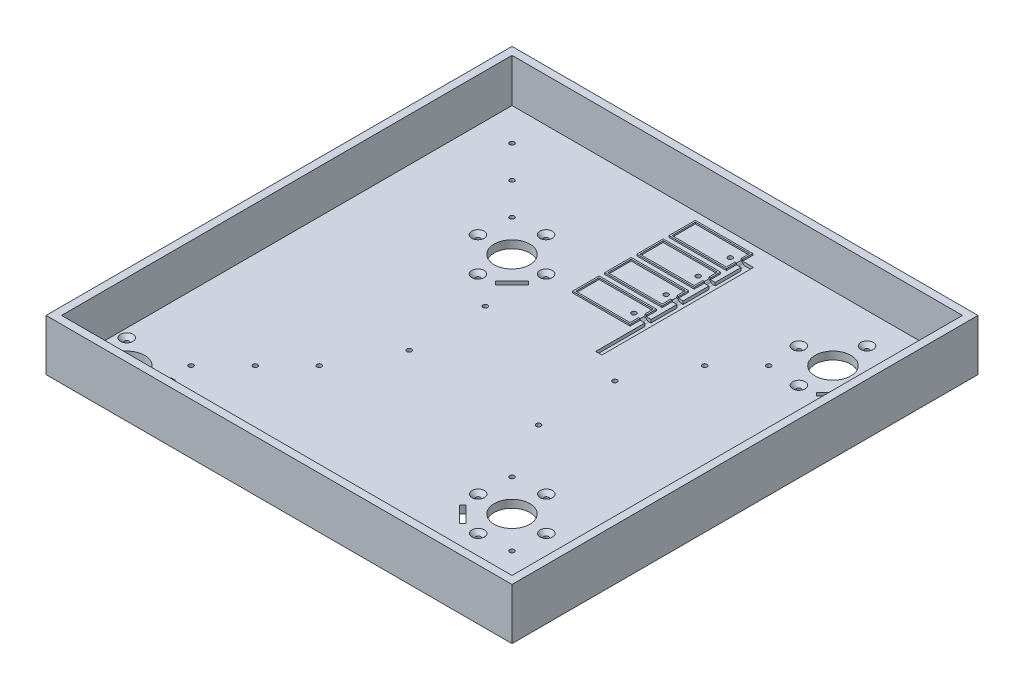
SolidWorks part; units mm, degrees
note: The reader was unsure of these and kept them because the rebuilt part matched: shared geometry of "Эскиз8<2>".
material "ABS"
ref_plane "Спереди" through (0, 0, 0) normal (0, 0, 1) x (1, 0, 0)
ref_plane "Сверху" through (0, 0, 0) normal (0, 1, 0) x (1, 0, 0)
ref_plane "Справа" through (0, 0, 0) normal (1, 0, 0) x (0, 0, -1)
other "Configuration Table"
sketch "Эскиз1" plane through (0, 0, 0) normal (0, 1, 0) x (1, 0, 0)
  line L0 (-136.1102, 103.5232) -> (-30.3617, 103.5232) construction
  line L1 (-136.1102, 103.5232) -> (163.8898, 103.5232)
  line L2 (-136.1102, 103.5232) -> (-136.1102, -196.4768)
  line L3 (-136.1102, -196.4768) -> (163.8898, -196.4768)
  line L4 (163.8898, 103.5232) -> (163.8898, -196.4768)
  line L5 (-136.1102, 103.5232) -> (-136.1102, -1.4471) construction
  line L8 (-30.5081, -2.079) -> (-35385.8471, 35353.2601) construction
  line L9 (-136.1102, 98.5232) -> (163.8898, 98.5232) construction
  line L10 (-131.1102, 103.5232) -> (-131.1102, -196.4768) construction
  line L11 (158.8898, 103.5232) -> (158.8898, -196.4768) construction
  line L12 (-136.1102, -191.4768) -> (163.8898, -191.4768) construction
  line L17 (-36.1102, 3.5232) -> (-131.1102, 3.5232) construction
  line L18 (-36.1102, 3.5232) -> (63.8898, 3.5232) construction
  line L19 (-36.1102, 3.5232) -> (-36.1102, -96.4768) construction
  line L20 (-36.1102, -96.4768) -> (63.8898, -96.4768) construction
  line L21 (63.8898, 3.5232) -> (63.8898, -96.4768) construction
  line L22 (-36.1102, -96.4768) -> (-131.1102, -96.4768) construction
  line L23 (-36.1102, 3.5232) -> (-36.1102, 98.5232) construction
  line L24 (63.8898, 3.5232) -> (158.8898, 3.5232) construction
  line L25 (63.8898, -96.4768) -> (158.8898, -96.4768) construction
  line L26 (63.8898, 3.5232) -> (63.8898, 98.5232) construction
  line L27 (63.8898, -96.4768) -> (63.8898, -191.4768) construction
  line L32 (-837.8814, -898.248) -> (34517.4576, 34457.0911) construction
  line L33 (-131.1102, -191.4768) -> (-89.1102, -149.4768) construction
  line L35 (-131.1102, -149.4768) -> (-131.1102, -191.4768) construction
  line L36 (-131.1102, -191.4768) -> (-89.1102, -191.4768) construction
  line L38 (-36.1102, -96.4768) -> (-36.1102, -191.4768) construction
  line L39 (-131.1102, -149.4768) -> (-89.1102, -149.4768) construction
  line L44 (-89.1102, -191.4768) -> (-89.1102, -149.4768) construction
  line L45 (-131.1102, -149.4768) -> (-89.1102, -191.4768) construction
  line L54 (-77.8295, 15.544) -> (-48.1311, 45.2425) construction
  line L71 (-48.1311, 45.2425) -> (-18.4326, 15.544) construction
  line L72 (-18.4326, 15.544) -> (-48.1311, -14.1545) construction
  line L73 (-77.8295, 15.544) -> (-48.1311, -14.1545) construction
  line L74 (-48.1311, -14.1545) -> (-48.1311, 45.2425) construction
  line L75 (-77.8295, 15.544) -> (-17.684, 15.544) construction
  line L76 (-48.1311, 22.044) -> (75.9106, 22.044) construction
  line L77 (-68.7786, 42.6915) -> (96.5581, 42.6915) construction
  line L78 (-89.4261, 63.339) -> (117.2056, 63.339) construction
  line L79 (-110.1092, 84.0221) -> (137.7881, 84.0211) construction
  line L80 (-33.2818, 0.6948) -> (-38.5851, -4.6085)
  line L81 (-38.5851, -4.6085) -> (-36.4638, -6.7299)
  line L86 (-27.9785, 5.9981) -> (-33.2818, 0.6948)
  line L91 (66.8596, -128.9763) -> (96.5581, -99.2778) construction
  line L97 (66.8596, -128.9763) -> (96.5581, -158.6748) construction
  line L98 (96.5581, -99.2778) -> (126.2566, -128.9763) construction
  line L99 (96.5581, -158.6748) -> (126.2566, -128.9763) construction
  line L100 (96.5581, -158.6748) -> (96.5581, -99.2778) construction
  line L101 (66.8596, -128.9763) -> (126.2566, -128.9763) construction
  line L102 (81.7088, -143.8256) -> (76.8333, -138.95)
  line L103 (76.8333, -138.95) -> (74.712, -141.0714)
  line L105 (74.712, -141.0714) -> (80.0153, -146.3747)
  line L106 (81.7088, -143.8256) -> (87.0121, -149.1289)
  line L107 (87.0121, -149.1289) -> (84.8908, -151.2502)
  line L108 (80.0153, -146.3747) -> (84.8908, -151.2502)
  line L109 (87.5071, 56.839) -> (117.2056, 86.5375) construction
  line L110 (87.5071, 56.839) -> (117.2056, 27.1406) construction
  line L111 (117.2056, 27.1406) -> (146.9041, 56.839) construction
  line L112 (146.9041, 56.839) -> (117.2056, 86.5375) construction
  line L113 (87.5071, 56.839) -> (146.9041, 56.839) construction
  line L114 (117.2056, 27.1406) -> (117.2056, 86.5375) construction
  line L115 (132.0548, 41.9898) -> (126.7515, 36.6865)
  line L116 (126.7515, 36.6865) -> (128.8729, 34.5652)
  line L117 (128.8729, 34.5652) -> (134.1762, 39.8685)
  line L119 (132.0548, 41.9898) -> (137.3581, 47.2931)
  line L120 (139.4795, 45.1718) -> (134.1762, 39.8685)
  line L121 (137.3581, 47.2931) -> (139.4795, 45.1718)
  line L122 (-89.1102, -170.4768) -> (-89.1102, -162.9768)
  line L123 (-89.1102, -162.9768) -> (-86.1102, -162.9768)
  line L124 (-86.1102, -162.9768) -> (-86.1102, -168.2374)
  line L125 (-86.1102, -168.2374) -> (-86.1102, -177.9768)
  line L126 (-86.1102, -177.9768) -> (-89.1102, -177.9768)
  line L127 (-89.1102, -177.9768) -> (-89.1102, -170.4768)
  line L128 (-36.4638, -6.7299) -> (-25.8572, 3.8767)
  line L129 (-30.7602, -73.9968) -> (58.5398, -73.9968) construction
  line L130 (-30.7602, -73.9968) -> (-30.7602, -18.9568) construction
  line L131 (-30.7602, -18.9568) -> (58.5398, -18.9568) construction
  line L132 (58.5398, -73.9968) -> (58.5398, -18.9568) construction
  line L133 (-30.7602, -73.9968) -> (58.5398, -18.9568) construction
  line L134 (-30.7602, -18.9568) -> (58.5398, -73.9968) construction
  line L135 (-25.8572, 3.8767) -> (-27.9785, 5.9981)
  line L136 (82.4106, 15.544) -> (82.4106, -108.4976) construction
  line L137 (103.0581, 36.1915) -> (103.0559, -128.9763) construction
  line L138 (123.7056, 56.839) -> (123.7056, -149.7927) construction
  line L139 (144.3885, 77.5219) -> (144.3885, -170.4755) construction
  line L140 (-48.1311, -114.9976) -> (75.9106, -114.9976) construction
  line L141 (-68.7786, -135.6451) -> (96.5581, -135.6451) construction
  line L142 (-89.4261, -156.2927) -> (117.2056, -156.2927) construction
  line L143 (-110.1102, -176.9768) -> (137.8885, -176.9755) construction
  line L144 (-54.6311, 15.544) -> (-54.6311, -108.4976) construction
  line L145 (-75.2786, 36.1915) -> (-75.2786, -129.1451) construction
  line L146 (-95.9261, 56.839) -> (-95.9184, -149.4768) construction
  line L147 (-116.6092, 77.5221) -> (-116.6092, -170.5948) construction
  line L148 (-1.1106, 84.0217) -> (-1.1106, 76.5217) construction
  line L157 (-1.1102, 29.544) -> (28.8898, 29.544) construction
  line L159 (-1.1102, 29.544) -> (-1.1102, 14.544) construction
  line L160 (-1.1102, 14.544) -> (28.8898, 14.544) construction
  line L161 (28.8898, 29.544) -> (28.8898, 14.544) construction
  line L162 (-1.1106, 50.1915) -> (28.8894, 50.1915) construction
  line L163 (-1.1106, 50.1915) -> (-1.1106, 35.1915) construction
  line L164 (-1.1106, 35.1915) -> (28.8894, 35.1915) construction
  line L165 (28.8894, 50.1915) -> (28.8894, 35.1915) construction
  line L166 (-1.1106, 70.839) -> (28.8894, 70.839) construction
  line L167 (-1.1106, 70.839) -> (-1.1106, 55.839) construction
  line L168 (-1.1106, 55.839) -> (28.8894, 55.839) construction
  line L169 (28.8894, 70.839) -> (28.8894, 55.839) construction
  line L174 (-1.1106, 84.0217) -> (-1.1106, 91.5217) construction
  line L175 (-1.1106, 91.5217) -> (28.8894, 91.5217) construction
  line L176 (28.8894, 91.5217) -> (28.8894, 76.5217) construction
  line L177 (28.8894, 76.5217) -> (-1.1106, 76.5217) construction
  line L178 (-131.1102, -86.4768) -> (-36.1102, -86.4768) construction
  line L179 (-131.1102, -76.4768) -> (-36.1102, -76.4768) construction
  line L180 (-131.1102, -66.4768) -> (-36.1102, -66.4768) construction
  line L181 (-131.1102, -56.4768) -> (-36.1102, -56.4768) construction
  line L182 (-131.1102, -46.4768) -> (-36.1102, -46.4768) construction
  line L183 (-131.1102, -36.4768) -> (-36.1102, -36.4768) construction
  line L184 (-131.1102, -26.4768) -> (-36.1102, -26.4768) construction
  line L185 (-131.1102, -16.4768) -> (-36.1102, -16.4768) construction
  line L186 (-131.1102, -6.4768) -> (-36.1102, -6.4768) construction
  circle A49 centre (-48.1311, 15.544) radius 11.5
  circle A51 centre (-89.4261, 56.839) radius 1.5
  circle A52 centre (-110.1092, 77.5221) radius 1.5
  circle A53 centre (-110.1102, -170.4768) radius 11.5
  circle A54 centre (-125.6102, -154.9768) radius 1.5
  circle A55 centre (-125.6102, -185.9768) radius 1.5
  circle A56 centre (-94.6102, -185.9768) radius 1.5
  circle A57 centre (-89.4261, -149.7927) radius 1.5
  circle A58 centre (-68.7786, -129.1451) radius 1.5
  circle A59 centre (-48.1311, -108.4976) radius 1.5
  circle A60 centre (-110.1102, -170.4768) radius 6.5 construction
  circle A61 centre (-48.1311, -108.4976) radius 6.5 construction
  circle A62 centre (-68.7786, -129.1451) radius 6.5 construction
  circle A63 centre (-89.4261, -149.7927) radius 6.5 construction
  circle A64 centre (-48.1311, 15.544) radius 6.5 construction
  circle A65 centre (-68.7786, 36.1915) radius 1.5
  circle A66 centre (-68.7786, 36.1915) radius 6.5 construction
  circle A67 centre (-89.4261, 56.839) radius 6.5 construction
  circle A68 centre (-110.1092, 77.5221) radius 6.5 construction
  circle A69 centre (-48.1311, 37.4643) radius 1.5
  circle A70 centre (-70.0514, 15.544) radius 1.5
  circle A71 centre (-26.2108, 15.544) radius 1.5
  circle A72 centre (-48.1311, -6.3763) radius 1.5
  circle A73 centre (75.9106, -108.4976) radius 1.5
  circle A74 centre (96.5581, -129.1451) radius 11.5
  circle A75 centre (117.2056, -149.7927) radius 1.5
  circle A76 centre (137.8885, -170.4755) radius 1.5
  circle A77 centre (75.9106, -108.4976) radius 6.5 construction
  circle A78 centre (96.5581, -129.1451) radius 6.5 construction
  circle A79 centre (117.2056, -149.7927) radius 6.5 construction
  circle A80 centre (137.8885, -170.4755) radius 6.5 construction
  circle A81 centre (96.5581, -107.056) radius 1.5
  circle A82 centre (74.6378, -128.9763) radius 1.5
  circle A83 centre (96.5581, -150.8966) radius 1.5
  circle A84 centre (118.4784, -128.9763) radius 1.5
  circle A85 centre (75.9106, 15.544) radius 1.5
  circle A86 centre (96.5581, 36.1915) radius 1.5
  circle A87 centre (117.2056, 56.839) radius 11.5
  circle A88 centre (137.8885, 77.5219) radius 1.5
  circle A89 centre (75.9106, 15.544) radius 6.5 construction
  circle A90 centre (96.5581, 36.1915) radius 6.5 construction
  circle A91 centre (137.8885, 77.5219) radius 6.5 construction
  circle A92 centre (117.2056, 78.7594) radius 1.5
  circle A93 centre (95.2853, 56.839) radius 1.5
  circle A94 centre (139.1259, 56.839) radius 1.5
  circle A95 centre (117.2056, 34.9187) radius 1.5
  circle A96 centre (-27.7602, -21.9568) radius 1.5
  circle A97 centre (-27.7602, -70.9968) radius 1.5
  circle A98 centre (55.5398, -70.9968) radius 1.5
  circle A99 centre (55.5398, -21.9568) radius 1.5
  circle A100 centre (117.2056, 56.839) radius 6.5 construction
  circle A101 centre (23.8894, 84.0216) radius 1.5
  circle A102 centre (23.8894, 63.339) radius 1.5
  circle A103 centre (23.8894, 42.6915) radius 1.5
  circle A104 centre (23.8898, 22.044) radius 1.5
  point P20 (-131.1102, 98.5232)
  point P43 (-110.1102, -170.4768)
  point P65 (-48.1311, 15.544)
  point P72 (158.8898, 98.5232)
  point P76 (158.8898, -191.4768)
  point P113 (96.5581, -128.9763)
  point P146 (117.2056, 56.839)
  point P168 (13.8898, -46.4768)
  point P169 (13.8898, -46.4768)
  point P214 (12.3478, 20.3373)
  dimension "D5" = 100
  dimension "D17" = 95
  dimension "D29" = 5.5
  dimension "D31" = 5.5
  dimension "D33" = 17
  dimension "D36" = 21
  dimension "D50" = 29.2503
  dimension "D51" = 5.5
  dimension "D53" = 5.5
  dimension "D54" = 5.5
  dimension "D65" = 7.5
  dimension "D67" = 3
  dimension "D69" = 29.2
  dimension "D71" = 29.25
  dimension "D80" = 0
  dimension "D84" = 5.5
  dimension "D112" = 5.5
  dimension "D116" = 3
  dimension "D9" = 42
  dimension "D26" = 5.5
  dimension "D28" = 5.5
  dimension "D30" = 5.5
  dimension "D32" = 17
  dimension "D34" = 29.7
  dimension "D55" = 5.5
  dimension "D57" = 5.5
  dimension "D68" = 17
  dimension "D72" = 42
  dimension "D81" = 5.5
  dimension "D83" = 5.5
  dimension "D85" = 5.5
  dimension "D87" = 5.5
  dimension "D92" = 17
  dimension "D96" = 0
  dimension "D105" = 5.5
  dimension "D108" = 5.5
  dimension "D110" = 5.5
  dimension "D122" = 3
  dimension "D124" = 3
  dimension "D126" = 3
  dimension "D128" = 3
  dimension "D131" = 13
  dimension "D132" = 13
  dimension "D133" = 13
  dimension "D134" = 13
  dimension "D135" = 13
  dimension "D136" = 13
  dimension "D137" = 13
  dimension "D138" = 13
  dimension "D139" = 13
  dimension "D140" = 13
  dimension "D141" = 13
  dimension "D142" = 13
  dimension "D143" = 13
  dimension "D144" = 13
  dimension "D145" = 13
  dimension "D146" = 13
  dimension "D162" = 5
  dimension "D163" = 5
  dimension "D164" = 5
  dimension "D165" = 5
  dimension "D1" = 300
  dimension "D2" = 300
  dimension "D3" = 5
  dimension "D4" = 5
  dimension "D6" = 5
  dimension "D7" = 5
  dimension "D8" = 100
  dimension "D10" = 42
  dimension "D11" = 21
  dimension "D12" = 5
  dimension "D13" = 5
  dimension "D15" = 95
  dimension "D18" = 95
  dimension "D19" = 95
  dimension "D20" = 21
  dimension "D21" = 0
  dimension "D22" = 21
  dimension "D23" = 21
  dimension "D24" = 21
  dimension "D25" = 21
  dimension "D27" = 5.5
  dimension "D35" = 21
  dimension "D37" = 0
  dimension "D38" = 205.061
  dimension "D40" = 0
  dimension "D41" = 29.2
  dimension "D42" = 29.2
  dimension "D43" = 29.2518
  dimension "D44" = 29.2
  dimension "D45" = 29.2
  dimension "D46" = 5
  dimension "D47" = 5
  dimension "D48" = 5
  dimension "D49" = 5
  dimension "D52" = 5.5
  dimension "D56" = 5.5
  dimension "D58" = 5.5
  dimension "D59" = 95
  dimension "D60" = 205.061
  dimension "D61" = 205.061
  dimension "D62" = 0
  dimension "D63" = 5
  dimension "D64" = 5
  dimension "D66" = 7.5
  dimension "D70" = 29.2
  dimension "D73" = 42
  dimension "D74" = 42
  dimension "D75" = 42
  dimension "D76" = 29.6985
  dimension "D77" = 29.6985
  dimension "D78" = 29.6985
  dimension "D79" = 0
  dimension "D82" = 5.5
  dimension "D86" = 5.5
  dimension "D88" = 5.5
  dimension "D89" = 3
  dimension "D90" = 7.5
  dimension "D91" = 7.5
  dimension "D93" = 29.2
  dimension "D94" = 29.2
  dimension "D95" = 29.25
  dimension "D97" = 42
  dimension "D98" = 42
  dimension "D99" = 42
  dimension "D100" = 42
  dimension "D101" = 21
  dimension "D102" = 29.6985
  dimension "D103" = 29.6985
  dimension "D104" = 0
  dimension "D106" = 5.5
  dimension "D107" = 5.5
  dimension "D109" = 5.5
  dimension "D111" = 5.5
  dimension "D113" = 5.5
  dimension "D114" = 7.5
  dimension "D115" = 3
  dimension "D117" = 7.5
  dimension "D118" = 7.5
  dimension "D119" = 0
  dimension "D120" = 89.3
  dimension "D121" = 55.04
  dimension "D123" = 3
  dimension "D125" = 3
  dimension "D127" = 3
  dimension "D129" = 3
  dimension "D130" = 15
  dimension "D39" = 205.061
  dimension "D147" = 10
  dimension "D148" = 9
  dimension "D152" = 30
  dimension "D153" = 15
  dimension "D154" = 7.5
  dimension "D155" = 35
  dimension "D156" = 30
  dimension "D157" = 15
  dimension "D158" = 7.5
  dimension "D159" = 30
  dimension "D160" = 15
  dimension "D161" = 7.5
extrude "Бобышка-Вытянуть1" add sketch "Эскиз1" along normal blind 5
sketch "Эскиз2" plane through (0, 5, 0) normal (0, 1, 0) x (1, 0, 0)
  line L0 (-136.1102, -196.4768) -> (163.8898, -196.4768) construction
  line L1 (-136.1102, 103.5232) -> (-131.1102, 103.5232)
  line L2 (-136.1102, 103.5232) -> (-136.1102, -196.4768)
  line L3 (-136.1102, -196.4768) -> (-131.1102, -196.4768)
  line L4 (-131.1102, 103.5232) -> (-131.1102, -196.4768)
  dimension "D1" = 5
extrude "Бобышка-Вытянуть2" add sketch "Эскиз2" along normal blind 28
sketch "Эскиз3" plane through (0, 5, 0) normal (0, 1, 0) x (1, 0, 0)
  line L0 (-131.1102, -196.4768) -> (163.8898, -196.4768) construction
  line L1 (163.8898, 103.5232) -> (158.8898, 103.5232)
  line L2 (163.8898, 103.5232) -> (163.8898, -196.4768)
  line L3 (163.8898, -196.4768) -> (158.8898, -196.4768)
  line L4 (158.8898, 103.5232) -> (158.8898, -196.4768)
  dimension "D1" = 5
extrude "Бобышка-Вытянуть3" add sketch "Эскиз3" along normal blind 28
sketch "Эскиз4" plane through (0, 5, 0) normal (0, 1, 0) x (1, 0, 0)
  line L0 (158.8898, 103.5232) -> (158.8898, -196.4768) construction
  line L1 (-131.1102, -196.4768) -> (158.8898, -196.4768)
  line L2 (-131.1102, -196.4768) -> (-131.1102, -191.4768)
  line L3 (-131.1102, -191.4768) -> (158.8898, -191.4768)
  line L4 (158.8898, -196.4768) -> (158.8898, -191.4768)
  dimension "D1" = 5
extrude "Бобышка-Вытянуть4" add sketch "Эскиз4" along normal blind 28
sketch "Эскиз5" plane through (0, 5, 0) normal (0, 1, 0) x (1, 0, 0)
  line L0 (158.8898, 103.5232) -> (158.8898, -191.4768) construction
  line L1 (-131.1102, 103.5232) -> (158.8898, 103.5232)
  line L2 (-131.1102, 103.5232) -> (-131.1102, 98.5232)
  line L3 (-131.1102, 98.5232) -> (158.8898, 98.5232)
  line L4 (158.8898, 103.5232) -> (158.8898, 98.5232)
  dimension "D1" = 5
extrude "Бобышка-Вытянуть5" add sketch "Эскиз5" along normal blind 28
chamfer "Фаска1" distance 2.5 angle 45 4 edges at (-48.1311, 5, 7.8763) (-26.2108, 5, -14.044) (-48.1311, 5, -35.9643) (-70.0514, 5, -14.044)
chamfer "Фаска2" distance 2.5 angle 45 4 edges at (117.2056, 5, -33.4187) (139.1259, 5, -55.339) (117.2056, 5, -77.2594) (95.2853, 5, -55.339)
chamfer "Фаска3" distance 2.5 angle 45 4 edges at (96.5581, 5, 152.3966) (74.6378, 5, 130.4763) (118.4784, 5, 130.4763) (96.5581, 5, 108.556)
chamfer "Фаска4" distance 2.5 angle 45 3 edges at (-94.6102, 5, 187.4768) (-125.6102, 5, 187.4768) (-125.6102, 5, 156.4768)
chamfer "Фаска5" distance 2.5 angle 45 16 edges at (137.8885, 0, -76.0219) (96.5581, 0, -34.6915) (75.9106, 0, -14.044) (137.8885, 0, 171.9755) (117.2056, 0, 151.2927) (75.9106, 0, 109.9976) (-27.7602, 0, 23.4568) (55.5398, 0, 23.4568) (55.5398, 0, 72.4968) (-27.7602, 0, 72.4968) (-48.1311, 0, 109.9976) (-68.7786, 0, 130.6451) (-89.4261, 0, 151.2927) (-68.7786, 0, -34.6915) (-89.4261, 0, -55.339) (-110.1092, 0, -76.0221)
sketch "Эскиз6" plane through (0, 5, 0) normal (0, 1, 0) x (1, 0, 0)
  line L0 (-131.1102, 98.5232) -> (158.8898, 98.5232) construction
  line L1 (28.8898, 91.5232) -> (-6.1102, 91.5232)
  line L2 (28.8898, 91.5232) -> (28.8898, 76.5232)
  line L3 (28.8898, 76.5232) -> (-6.1102, 76.5232)
  line L4 (-6.1102, 91.5232) -> (-6.1102, 76.5232)
  line L5 (158.8898, 98.5232) -> (158.8898, -191.4768) construction
  line L7 (-7.1102, 92.5232) -> (29.8898, 92.5232)
  line L8 (-7.1102, 92.5232) -> (-7.1102, 75.5232)
  line L9 (-7.1102, 75.5232) -> (29.8898, 75.5232)
  line L10 (29.8898, 92.5232) -> (29.8898, 75.5232)
  dimension "D1" = 35
  dimension "D2" = 15
  dimension "D3" = 7
  dimension "D4" = 130
  dimension "D5" = 1
  dimension "D6" = 1
  dimension "D7" = 1
  dimension "D8" = 1
extrude "Бобышка-Вытянуть6" add sketch "Эскиз6" along normal blind 1
sketch "Эскиз7" plane through (0, 5, 0) normal (0, 1, 0) x (1, 0, 0)
  line L0 (-6.1102, 76.5232) -> (28.8898, 76.5232) construction
  line L1 (-6.1102, 70.8432) -> (28.8898, 70.8432)
  line L2 (-6.1102, 70.8432) -> (-6.1102, 55.8432)
  line L3 (-6.1102, 55.8432) -> (28.8898, 55.8432)
  line L4 (28.8898, 70.8432) -> (28.8898, 55.8432)
  line L6 (-7.1102, 71.8432) -> (29.8898, 71.8432)
  line L7 (-7.1102, 71.8432) -> (-7.1102, 54.8432)
  line L8 (-7.1102, 54.8432) -> (29.8898, 54.8432)
  line L9 (29.8898, 71.8432) -> (29.8898, 54.8432)
  dimension "D5" = 1
  dimension "D6" = 1
  dimension "D1" = 15
  dimension "D2" = 5.68
  dimension "D3" = 1
  dimension "D4" = 1
extrude "Бобышка-Вытянуть7" add sketch "Эскиз7" along normal blind 1
sketch "Эскиз8" plane through (0, 5, 0) normal (0, 1, 0) x (1, 0, 0)
  line L1 (-6.1102, 50.1932) -> (28.8898, 50.1932)
  line L2 (-6.1102, 50.1932) -> (-6.1102, 35.1932)
  line L3 (-6.1102, 35.1932) -> (28.8898, 35.1932)
  line L4 (28.8898, 50.1932) -> (28.8898, 35.1932)
  line L5 (-6.1102, 55.8432) -> (28.8898, 55.8432) construction
  line L6 (-7.1102, 51.1932) -> (29.8898, 51.1932)
  line L7 (-7.1102, 51.1932) -> (-7.1102, 34.1932)
  line L8 (-7.1102, 34.1932) -> (29.8898, 34.1932)
  line L9 (29.8898, 51.1932) -> (29.8898, 34.1932)
  dimension "D1" = 35
  dimension "D2" = 15
  dimension "D5" = 1
  dimension "D6" = 1
  dimension "D7" = 1
  dimension "D4" = 1
  dimension "D3" = 5.65
extrude "Бобышка-Вытянуть8" add sketch "Эскиз8" along normal blind 1
extrude "Бобышка-Вытянуть9" add sketch "Эскиз8<2>" along normal blind 1
sketch "Эскиз8<2>" plane through (0, 5, 0) normal (0, 1, 0) x (1, 0, 0) same geometry as "Эскиз8"
sketch "Эскиз10" plane through (0, 5, 0) normal (0, 1, 0) x (1, 0, 0)
  line L0 (-6.1102, 35.1932) -> (28.8898, 35.1932) construction
  line L1 (-6.1102, 29.5432) -> (28.8898, 29.5432)
  line L2 (-6.1102, 29.5432) -> (-6.1102, 14.5432)
  line L3 (-6.1102, 14.5432) -> (28.8898, 14.5432)
  line L4 (28.8898, 29.5432) -> (28.8898, 14.5432)
  line L6 (-7.1102, 30.5432) -> (29.8898, 30.5432)
  line L7 (-7.1102, 30.5432) -> (-7.1102, 13.5432)
  line L8 (-7.1102, 13.5432) -> (29.8898, 13.5432)
  line L9 (29.8898, 30.5432) -> (29.8898, 13.5432)
  dimension "D2" = 15
  dimension "D5" = 1
  dimension "D6" = 1
  dimension "D3" = 1
  dimension "D4" = 1
  dimension "D1" = 5.65
extrude "Бобышка-Вытянуть10" add sketch "Эскиз10" along normal blind 1
sketch "Эскиз11" plane through (0, 5, 0) normal (0, 1, 0) x (1, 0, 0)
  line L0 (29.8898, 75.5232) -> (29.8898, 92.5232) construction
  line L2 (29.8898, 84.0232) -> (29.8898, 82.0232)
  line L3 (29.8898, 82.0232) -> (36.8898, 82.0232)
  line L4 (36.8898, 84.9756) -> (36.8898, 82.0232)
  line L7 (29.8898, 84.0232) -> (29.8898, 86.0232)
  line L8 (29.8898, 86.0232) -> (36.8898, 86.0232)
  line L9 (36.8898, 84.9756) -> (36.8898, 86.0232)
  dimension "D1" = 2
  dimension "D2" = 2
  dimension "D3" = 7
extrude "Вырез-Вытянуть1" cut sketch "Эскиз11" against normal blind 2
sketch "Эскиз12" plane through (0, 6, 0) normal (0, 1, 0) x (1, 0, 0)
  line L0 (28.8898, 76.5232) -> (28.8898, 91.5232) construction
  line L1 (29.8898, 86.0232) -> (28.8898, 86.0232)
  line L2 (29.8898, 86.0232) -> (29.8898, 82.0232)
  line L3 (29.8898, 82.0232) -> (28.8898, 82.0232)
  line L4 (28.8898, 86.0232) -> (28.8898, 82.0232)
extrude "Вырез-Вытянуть2" cut sketch "Эскиз12" against normal blind 2
sketch "Эскиз13" plane through (0, 5, 0) normal (0, 1, 0) x (1, 0, 0)
  line L1 (36.8898, 82.0232) -> (32.8898, 82.0232)
  line L2 (36.8898, 82.0232) -> (36.8898, -11.6458)
  line L3 (36.8898, -11.6458) -> (32.8898, -11.6458)
  line L4 (32.8898, 82.0232) -> (32.8898, -11.6458)
  dimension "D1" = 4
extrude "Вырез-Вытянуть3" cut sketch "Эскиз13" against normal blind 2
sketch "Эскиз14" plane through (0, 6, 0) normal (0, 1, 0) x (1, 0, 0)
  line L0 (29.8898, 71.8432) -> (29.8898, 54.8432) construction
  line L1 (29.8898, 54.8432) -> (29.8898, 71.8432) construction
  line L2 (-7.1102, 54.8432) -> (29.8898, 54.8432) construction
  line L3 (28.8898, 55.8432) -> (28.8898, 70.8432) construction
  line L4 (28.8898, 55.8432) -> (28.8898, 70.8432) construction
  line L6 (28.8898, 63.3432) -> (28.8898, 65.3432)
  line L7 (28.8898, 65.3432) -> (29.8898, 65.3432)
  line L8 (29.8898, 63.3432) -> (29.8898, 65.3432)
  line L11 (28.8898, 63.3432) -> (28.8898, 61.3432)
  line L12 (28.8898, 61.3432) -> (29.8898, 61.3432)
  line L13 (29.8898, 63.3432) -> (29.8898, 61.3432)
  point P7 (28.8898, 63.3432)
  dimension "D1" = 2
  dimension "D2" = 2
extrude "Вырез-Вытянуть4" cut sketch "Эскиз14" against normal blind 2
sketch "Эскиз15" plane through (0, 5, 0) normal (0, 1, 0) x (1, 0, 0)
  line L0 (32.8898, 82.0232) -> (32.8898, -11.6458) construction
  line L1 (29.8898, 65.3432) -> (32.8898, 65.3432)
  line L2 (29.8898, 65.3432) -> (29.8898, 61.3432)
  line L3 (29.8898, 61.3432) -> (32.8898, 61.3432)
  line L4 (32.8898, 65.3432) -> (32.8898, 61.3432)
  dimension "D1" = 4
extrude "Вырез-Вытянуть5" cut sketch "Эскиз15" against normal blind 2
fillet "Скругление1" radius 2 1 edges at (28.8898, 4, -84.0232)
fillet "Скругление2" radius 2 3 edges at (29.8898, 3.5, -86.0232) (29.8898, 3, -84.0232) (29.8898, 3.5, -82.0232)
fillet "Скругление3" radius 2 1 edges at (29.8898, 4, -84.0232)
fillet "Скругление5" radius 2 1 edges at (28.8898, 4, -63.3432)
fillet "Скругление6" radius 2 1 edges at (29.8898, 3, -63.3432)
fillet "Скругление7" radius 2 1 edges at (29.8898, 4, -63.3432)
sketch "Эскиз16" plane through (0, 6, 0) normal (0, 1, 0) x (1, 0, 0)
  line L0 (29.8898, 34.1932) -> (29.8898, 51.1932) construction
  line L2 (29.8898, 42.6932) -> (29.8898, 44.6932)
  line L3 (29.8898, 44.6932) -> (28.8898, 44.6932)
  line L4 (28.8898, 42.6932) -> (28.8898, 44.6932)
  line L5 (28.8898, 35.1932) -> (28.8898, 50.1932) construction
  line L6 (29.8898, 34.1932) -> (29.8898, 51.1932) construction
  line L8 (28.8898, 42.6932) -> (28.8898, 40.6932)
  line L9 (28.8898, 40.6932) -> (29.8898, 40.6932)
  line L10 (29.8898, 42.6932) -> (29.8898, 40.6932)
  dimension "D1" = 2
  dimension "D2" = 2
extrude "Вырез-Вытянуть6" cut sketch "Эскиз16" against normal blind 2
sketch "Эскиз17" plane through (0, 5, 0) normal (0, 1, 0) x (1, 0, 0)
  line L0 (32.8898, 61.3432) -> (32.8898, -11.6458) construction
  line L1 (29.8898, 44.6932) -> (32.8898, 44.6932)
  line L2 (29.8898, 44.6932) -> (29.8898, 40.6891)
  line L3 (29.8898, 40.6891) -> (32.8898, 40.6891)
  line L4 (32.8898, 44.6932) -> (32.8898, 40.6891)
extrude "Вырез-Вытянуть8" cut sketch "Эскиз17" against normal blind 2
fillet "Скругление10" radius 2 1 edges at (28.8898, 4, -42.6932)
fillet "Скругление11" radius 2 1 edges at (29.8898, 3, -42.6911)
fillet "Скругление12" radius 2 1 edges at (30.2317, 3.8816, -42.6932)
sketch "Эскиз18" plane through (0, 6, 0) normal (0, 1, 0) x (1, 0, 0)
  line L0 (29.8898, 13.5432) -> (29.8898, 30.5432) construction
  line L2 (29.8898, 22.0432) -> (29.8898, 24.0432)
  line L3 (29.8898, 24.0432) -> (28.8898, 24.0432)
  line L4 (28.8898, 22.0432) -> (28.8898, 24.0432)
  line L5 (28.8898, 14.5432) -> (28.8898, 29.5432) construction
  line L8 (29.8898, 22.0432) -> (29.8898, 20.0432)
  line L9 (29.8898, 20.0432) -> (28.8898, 20.0432)
  line L10 (28.8898, 22.0432) -> (28.8898, 20.0432)
  dimension "D1" = 2
  dimension "D2" = 2
extrude "Вырез-Вытянуть9" cut sketch "Эскиз18" against normal blind 2
sketch "Эскиз19" plane through (0, 5, 0) normal (0, 1, 0) x (1, 0, 0)
  line L0 (32.8898, 40.6891) -> (32.8898, -11.6458) construction
  line L1 (29.8898, 24.0432) -> (32.8898, 24.0432)
  line L2 (29.8898, 24.0432) -> (29.8898, 20.047)
  line L3 (29.8898, 20.047) -> (32.8898, 20.047)
  line L4 (32.8898, 24.0432) -> (32.8898, 20.047)
extrude "Вырез-Вытянуть10" cut sketch "Эскиз19" against normal blind 2
fillet "Скругление15" radius 2 1 edges at (29.8898, 3, -22.0451)
fillet "Скругление17" radius 1 1 edges at (28.8898, 4, -22.0432)
fillet "Скругление18" radius 2 1 edges at (29.8898, 4, -22.0451)
equation "\"D6@Эскиз6\"=\"D5@Эскиз6\""
equation "\"D7@Эскиз6\"=\"D5@Эскиз6\""
equation "\"D8@Эскиз6\"=\"D5@Эскиз6\""
equation "\"D4@Эскиз7\"=\"D3@Эскиз7\""
equation "\"D5@Эскиз7\"=\"D3@Эскиз7\""
equation "\"D6@Эскиз7\"=\"D3@Эскиз7\""
equation "\"D5@Эскиз8\"=\"D4@Эскиз8\""
equation "\"D6@Эскиз8\"=\"D4@Эскиз8\""
equation "\"D7@Эскиз8\"=\"D4@Эскиз8\""
equation "\"D4@Эскиз10\"=\"D3@Эскиз10\""
equation "\"D5@Эскиз10\"=\"D3@Эскиз10\""
equation "\"D6@Эскиз10\"=\"D3@Эскиз10\""
